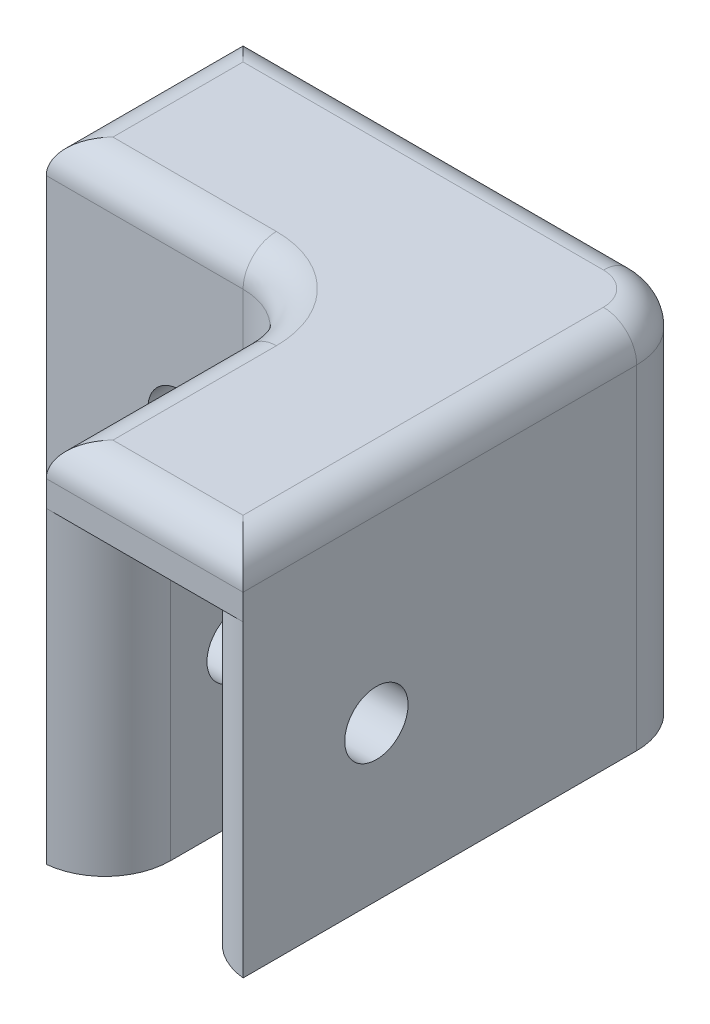
SolidWorks part; units mm, degrees
ref_plane "Front Plane" through (0, 0, 0) normal (0, 0, 1) x (1, 0, 0)
ref_plane "Top Plane" through (0, 0, 0) normal (0, 1, 0) x (1, 0, 0)
ref_plane "Right Plane" through (0, 0, 0) normal (1, 0, 0) x (0, 0, -1)
sketch "Sketch1" plane through (0, 0, 0) normal (0, 1, 0) x (1, 0, 0)
  line L0 (0, 0) -> (-35, 0)
  line L1 (0, 0) -> (0, -35)
  line L2 (-35, 0) -> (-35, -15)
  line L3 (-35, -15) -> (-15, -15)
  line L4 (-15, -15) -> (-15, -35)
  line L5 (-15, -35) -> (0, -35)
  dimension "D1" = 15
  dimension "D2" = 15
  dimension "D3" = 35
  dimension "D4" = 35
extrude "Boss-Extrude1" add sketch "Sketch1" along normal blind 28
sketch "Sketch2" plane through (0, 0, 0) normal (0, -1, 0) x (1, 0, 0)
  line L0 (-35, 4.5) -> (-4.5, 4.5)
  line L1 (-35, 0) -> (-35, 15) construction
  line L2 (-4.5, 4.5) -> (-4.5, 35)
  line L3 (-15, 35) -> (0, 35) construction
  line L4 (-4.5, 35) -> (-10.5, 35)
  line L5 (-10.5, 35) -> (-10.5, 10.5)
  line L6 (-10.5, 10.5) -> (-35, 10.5)
  line L7 (-35, 10.5) -> (-35, 4.5)
  line L8 (-35, 15) -> (-15, 15) construction
  point P4 (-7.5, 35)
  point P11 (-7.5, 35)
  point P13 (-35, 7.5)
  point P14 (-35, 7.5)
  dimension "D1" = 6
  dimension "D2" = 6
extrude "Cut-Extrude1" cut sketch "Sketch2" against normal blind 23.5
fillet "Fillet1" radius 5 2 edges at (-10.5, 11.75, 10.5) (-4.5, 11.75, 4.5)
fillet "Fillet3" radius 5 4 edges at (-4.5, 11.75, 35) (-10.5, 11.75, 35) (-35, 11.75, 10.5) (-35, 11.75, 4.5)
fillet "Fillet4" radius 5 2 edges at (0, 14, 0) (-15, 14, 15)
sketch "Sketch3" plane through (0, 0, 0) normal (1, 0, 0) x (0, 0, -1)
  line L1 (-35, 23.5) -> (-35, 0) construction
  circle A0 centre (-24.84, 11.75) radius 2.413
  point P0 (-24.84, 11.75)
  point P7 (-35, 11.75)
  dimension "D1" = 4.826
  dimension "D2" = 10.16
sketch "Sketch4" plane through (0, 0, 0) normal (0, 0, -1) x (-1, 0, 0)
  line L0 (5, 28) -> (5, 0) construction
  line L2 (35, 23.5) -> (35, 0) construction
  circle A0 centre (24.84, 14) radius 2.413
  point P0 (24.84, 14)
  point P5 (5, 14)
  dimension "D2" = 4.826
  dimension "D1" = 10.16
extrude "Cut-Extrude2" cut sketch "Sketch3" against normal through all
extrude "Cut-Extrude3" cut sketch "Sketch4" against normal through all
fillet "Fillet5" radius 2.54 8 edges at (-7.5, 28, 35) (-15, 28, 27.5) (-16.4645, 28, 16.4645) (-27.5, 28, 15) (-35, 28, 7.5) (-20, 28, 0) (-1.4645, 28, 1.4645) (0, 28, 20)
